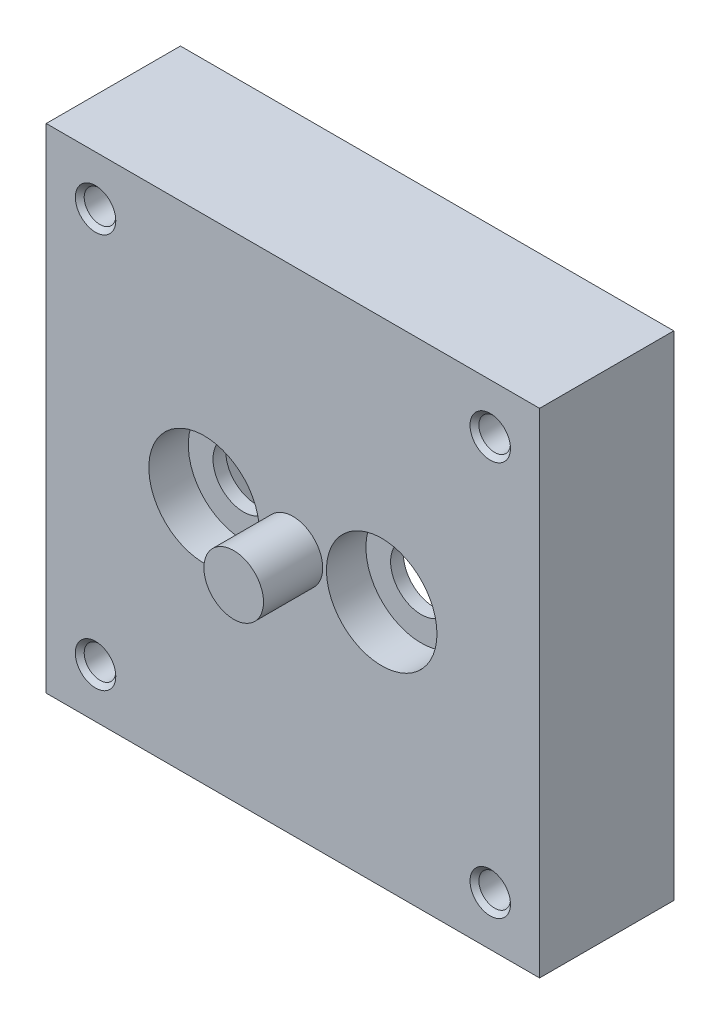
SolidWorks part; units mm, degrees
ref_plane "前视基准面" through (0, 0, 0) normal (0, 0, 1) x (1, 0, 0)
ref_plane "上视基准面" through (0, 0, 0) normal (0, 1, 0) x (1, 0, 0)
ref_plane "右视基准面" through (0, 0, 0) normal (1, 0, 0) x (0, 0, -1)
other "Configuration Table"
sketch "草图1" plane through (0, 0, 0) normal (0, 0, 1) x (1, 0, 0)
  line L1 (-12.5, 12.5) -> (12.5, 12.5)
  line L2 (-12.5, 12.5) -> (-12.5, -12.5)
  line L3 (-12.5, -12.5) -> (12.5, -12.5)
  line L4 (12.5, 12.5) -> (12.5, -12.5)
  line L5 (0, -12.5) -> (0, 12.5) construction
  line L6 (-12.5, 0) -> (12.5, 0) construction
  circle A0 centre (0, 0) radius 1.5
  point P0 (0, 0)
  dimension "D3" = 3
  dimension "D1" = 25
  dimension "D2" = 25
extrude "凸台-拉伸1" add sketch "草图1" along normal blind 7.65 contours L4 L1 L2 L3 A0 | A0 region at (0, 12.1464, 0) region at (0, 0, 0)
sketch "草图2" plane through (0, 0, 7.65) normal (0, 0, 1) x (1, 0, 0)
  circle A0 centre (0, 0) radius 1.51
  dimension "D1" = 3.02
extrude "凸台-拉伸2" add sketch "草图2" along normal blind 3
sketch "草图3" plane through (0, 0, 0) normal (0, 0, -1) x (-1, 0, 0)
  circle A0 centre (0, 0) radius 7.5
  dimension "D1" = 15
extrude "切除-拉伸1" cut sketch "草图3" against normal blind 5
sketch "草图4" plane through (0, 0, 7.65) normal (0, 0, 1) x (1, 0, 0)
  line L0 (0, 0) -> (0, 6.349) construction
  circle A0 centre (4.5, 0) radius 2.8
  circle A1 centre (-4.5, 0) radius 2.8
  dimension "D1" = 5.6
  dimension "D2" = 4.5
extrude "切除-拉伸2" cut sketch "草图4" against normal blind 2
sketch "草图5" plane through (0, 0, 5.65) normal (0, 0, 1) x (1, 0, 0)
  circle A0 centre (4.5, 0) radius 1.55
  circle A1 centre (-4.5, 0) radius 1.55
  dimension "D1" = 3.1
extrude "切除-拉伸3" cut sketch "草图5" against normal blind 2
sketch "草图6" plane through (-12.5, 0, 0) normal (-1, 0, 0) x (0, 0, 1)
  line L0 (0, 12.5) -> (0, -12.5) construction
  line L1 (-6.7432, 15.5492) -> (0.85, 15.5492)
  line L2 (-6.7432, 15.5492) -> (-6.7432, -15.1026)
  line L3 (-6.7432, -15.1026) -> (0.85, -15.1026)
  line L4 (0.85, 15.5492) -> (0.85, -15.1026)
  dimension "D1" = 0.85
extrude "切除-拉伸4" cut sketch "草图6" against normal through all
sketch "草图7" plane through (0, 0, 0.85) normal (0, 0, -1) x (-1, 0, 0)
  circle A0 centre (0, 0) radius 10
  circle A1 centre (0, 0) radius 7.5
  circle M7 centre (0, 0) radius 7.5
  dimension "D1" = 20
extrude "凸台-拉伸3" add sketch "草图7" along normal blind 0.5 contours A0 M7 region at (9.7172, 0, 0.85)
fillet "圆角4" radius 2 1 edges at (0, 10, 0.85)
hole_wizard "M2 螺纹孔1" positions "草图8" profile "草图10" tap size "M2" standard "GB" end condition through all
sketch "草图8" plane through (0, 0, 7.65) normal (0, 0, 1) x (1, 0, 0)
  line L0 (0, -12.5) -> (0, -5.7351) construction
  line L1 (-12.5, -12.5) -> (12.5, -12.5) construction
  line L3 (12.5, 0) -> (9.1923, 0) construction
  line L4 (12.5, 12.5) -> (12.5, -12.5) construction
  point P0 (-10, 10)
  point P2 (10, 10)
  point P4 (-10, -10)
  point P6 (10, -10)
  dimension "D1" = 10
  dimension "D2" = 10
sketch "草图10" plane through (-10, 10, 7.65) normal (1, 0, 0) x (0, -1, 0)
  line L0 (0, 0) -> (0, 7.3)
  line L1 (0, 7.3) -> (0.8, 7.3)
  line L2 (0.8, 7.3) -> (0.8, 0.225)
  line L3 (0.8, 0.225) -> (1.025, 0)
  line L5 (1.025, 0) -> (0, 0)
  line L6 (-0.8, 0.225) -> (-1.025, 0) construction
  line L11 (0, -6.35) -> (0, 107.95) construction
  dimension "通孔螺纹孔钻头直径" = 1.6
  dimension "通孔螺纹孔钻头深度" = 7.3
  dimension "近端锥形沉头孔直径" = 2.05
  dimension "近端锥形沉头孔角度" = 90
cosmetic thread "孔螺蚊线1" parameters "D2"=2
cosmetic thread "孔螺蚊线2" parameters "D2"=2
cosmetic thread "孔螺蚊线3" parameters "D2"=2
cosmetic thread "孔螺蚊线4" parameters "D2"=2
